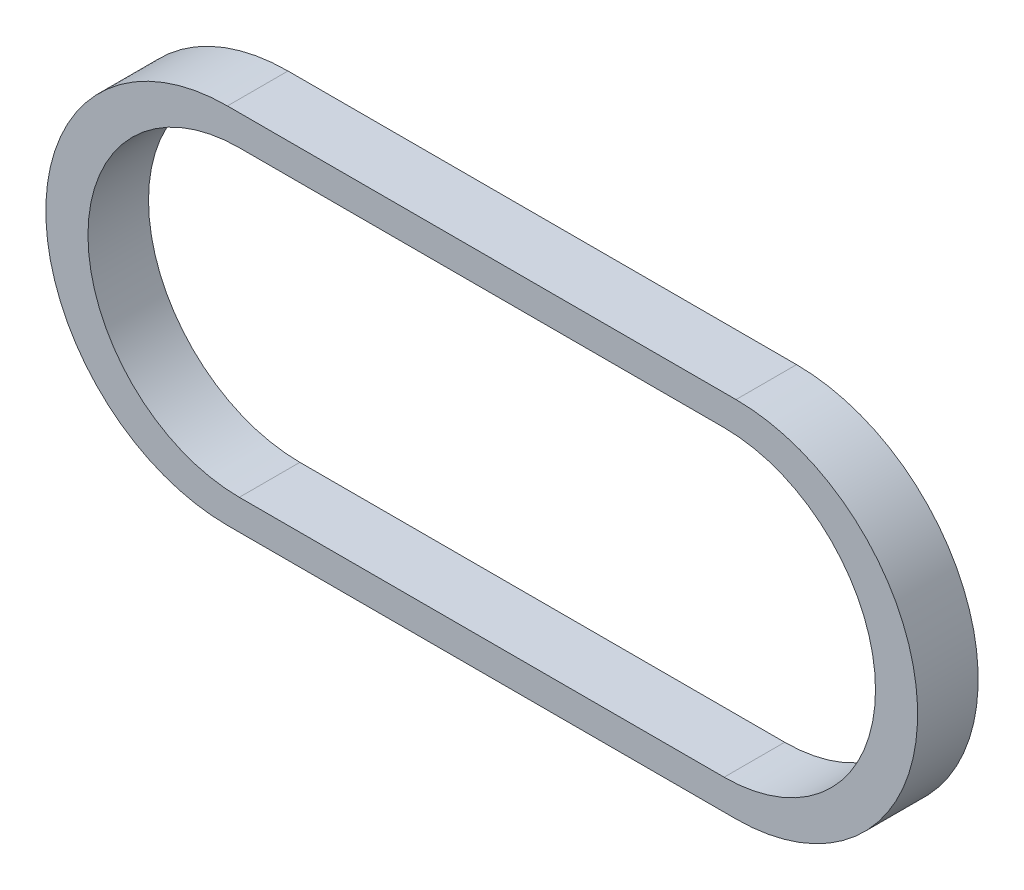
SolidWorks part; units mm, degrees
ref_plane "Front Plane" through (0, 0, 0) normal (0, 0, 1) x (1, 0, 0)
ref_plane "Top Plane" through (0, 0, 0) normal (0, 1, 0) x (1, 0, 0)
ref_plane "Right Plane" through (0, 0, 0) normal (1, 0, 0) x (0, 0, -1)
sketch "Sketch1" plane through (0, 0, 0) normal (0, 0, 1) x (1, 0, 0)
  line L0 (-210, 0) -> (210, 0) construction
  line L1 (-210, 150) -> (210, 150)
  line L2 (-210, -150) -> (210, -150)
  arc A0 (-210, 150) -> (-210, -150) centre (-210, 0) ccw
  arc A1 (210, -150) -> (210, 150) centre (210, 0) ccw
  point P2 (0, 0)
  dimension "D1" = 150
  dimension "D2" = 420
extrude "Boss-Extrude1" add sketch "Sketch1" along normal blind 50
sketch "Sketch2" plane through (0, 0, 50) normal (0, 0, 1) x (1, 0, 0)
  line L0 (200.1935, 0) -> (-200.1935, 0) construction
  line L1 (200.1935, -125) -> (-200.1935, -125)
  line L2 (200.1935, 125) -> (-200.1935, 125)
  arc A0 (200.1935, -125) -> (200.1935, 125) centre (200.1935, 0) ccw
  arc A1 (-200.1935, 125) -> (-200.1935, -125) centre (-200.1935, 0) ccw
  point P3 (0, 0)
  dimension "D1" = 125
  dimension "D2" = 400.387
extrude "Cut-Extrude1" cut sketch "Sketch2" against normal blind 50
